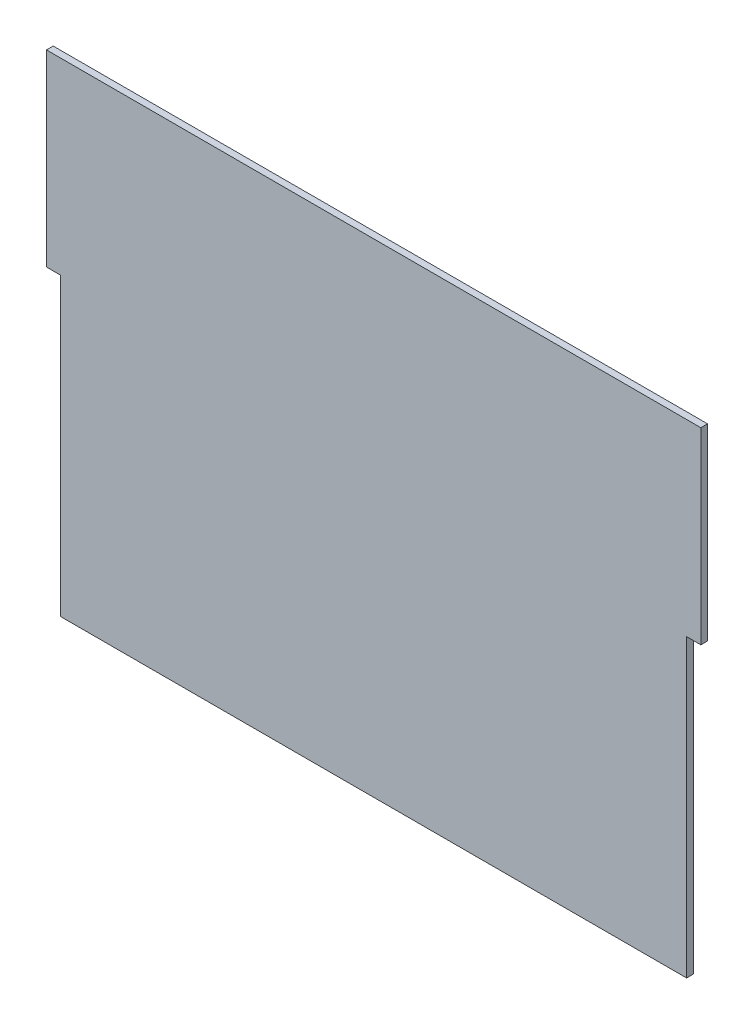
SolidWorks part; units mm, degrees
ref_plane "Front Plane" through (0, 0, 0) normal (0, 0, 1) x (1, 0, 0)
ref_plane "Top Plane" through (0, 0, 0) normal (0, 1, 0) x (1, 0, 0)
ref_plane "Right Plane" through (0, 0, 0) normal (1, 0, 0) x (0, 0, -1)
sketch "Sketch1" plane through (0, 0, 0) normal (0, 0, 1) x (1, 0, 0)
  line L0 (-146.05, 107.95) -> (146.05, 107.95)
  line L1 (146.05, 107.95) -> (146.05, 95.25)
  line L2 (146.05, 95.25) -> (139.7, 95.25)
  line L3 (139.7, 95.25) -> (139.7, -107.95)
  line L4 (139.7, -107.95) -> (-139.7, -107.95)
  line L5 (-139.7, -107.95) -> (-139.7, 95.25)
  line L6 (-139.7, 95.25) -> (-146.05, 95.25)
  line L7 (-146.05, 95.25) -> (-146.05, 107.95)
  line L8 (0, 107.95) -> (0, -107.95) construction
  line L10 (-146.05, 95.25) -> (-139.7, 95.25)
  line L11 (-146.05, 95.25) -> (-146.05, 24.003)
  line L12 (-146.05, 24.003) -> (-139.7, 24.003)
  line L13 (-139.7, 95.25) -> (-139.7, 24.003)
  line L14 (146.05, 95.25) -> (139.7, 95.25)
  line L15 (146.05, 95.25) -> (146.05, 24.003)
  line L16 (146.05, 24.003) -> (139.7, 24.003)
  line L17 (139.7, 95.25) -> (139.7, 24.003)
  point P10 (0, 0)
  dimension "D1" = 203.2
  dimension "D2" = 279.4
  dimension "D3" = 6.35
  dimension "D4" = 12.7
  dimension "D5" = 71.247
extrude "Boss-Extrude1" add sketch "Sketch1" along normal blind 2.9972 contours L8 L0 L7 L6 L5 L4 | L11 L12 L5 L6 | L0 L8 L4 L3 L2 L1 | L16 L15 L2 L3 region at (-70.0447, 0.2709, 0) region at (70.0447, 0.2709, 0) region at (-142.875, 59.6265, 0) region at (142.875, 59.6265, 0)
equation "\"wallthickness\"= .118in"
equation "\"floorThickness\"= .220in"
equation "\"D1@Boss-Extrude1\"=\"wallthickness\""
